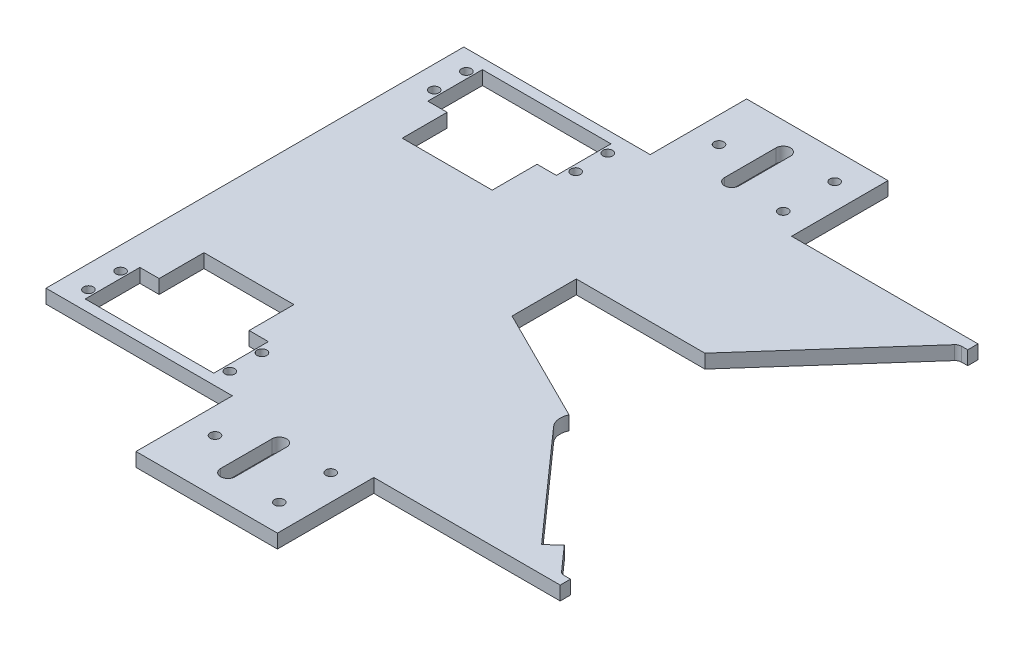
SolidWorks part; units mm, degrees
ref_plane "Front Plane" through (0, 0, 0) normal (0, 0, 1) x (1, 0, 0)
ref_plane "Top Plane" through (0, 0, 0) normal (0, 1, 0) x (1, 0, 0)
ref_plane "Right Plane" through (0, 0, 0) normal (1, 0, 0) x (0, 0, -1)
sketch "Sketch2" plane through (0, 0, 0) normal (0, 1, 0) x (1, 0, 0)
  line L2 (0, 0) -> (0, 65)
  line L3 (0, 65) -> (58, 65)
  line L4 (160, 0) -> (160, 65)
  line L8 (0, 0) -> (160, 0)
  line L9 (102, 65) -> (160, 65)
  line L11 (102, 65) -> (102, 95)
  line L12 (58, 65) -> (58, 95)
  line L13 (58, 95) -> (102, 95)
  dimension "D1" = 65
  dimension "D2" = 160
  dimension "D3" = 44
  dimension "D4" = 30
extrude "Boss-Extrude1" add sketch "Sketch2" along normal blind 4.3
mirror "Mirror1" about plane through (0, 4.3, 0) normal (0, 0, -1) of bodies 101
sketch "Sketch3" plane through (0, 4.3, 0) normal (0, 1, 0) x (1, 0, 0)
  line L0 (160, 61.8) -> (160, -61.8)
  line L1 (120.0126, 20) -> (157.1565, 61.8)
  line L3 (80.0126, 0) -> (80.0126, 20)
  line L4 (80.0126, 20) -> (120.0126, 20)
  line L12 (160, 65) -> (102, 65)
  line L13 (102, 65) -> (102, 95)
  line L15 (102, 95) -> (58, 95)
  line L16 (58, 65) -> (0, 65)
  line L17 (0, 65) -> (0, -65)
  line L18 (0, -65) -> (58, -65)
  line L20 (58, 95) -> (58, 65)
  line L22 (102, -65) -> (160, -65)
  line L23 (160, -65) -> (160, 65)
  line L36 (58, -65) -> (58, -95)
  line L38 (58, -95) -> (102, -95)
  line L39 (58, -95) -> (102, -95)
  line L40 (102, -95) -> (102, -65)
  line L42 (160, -61.8) -> (157.1556, -61.8)
  line L45 (160, 61.8) -> (157.1565, 61.8)
  line L48 (80.0126, 0) -> (120, -20)
  line L49 (120, -20) -> (157.1556, -61.8)
  line M24 (160, -65) -> (160, 65)
  dimension "D2" = 130
  dimension "D3" = 20
  dimension "D4" = 40
  dimension "D1" = 0
extrude "Cut-Extrude1" cut sketch "Sketch3" against normal blind 4.5 contours L48 L49 L1 L4 L3 M24 region at (132.7054, 4.3, -1.1594)
fillet "Fillet1" radius 2 2 edges at (157.1565, 2.15, -61.8) (157.1556, 2.15, 61.8)
ref_axis "Axis1" through (80, 4.3, 95) along (0, 0, -1)
sketch "Sketch4" plane through (0, 4.3, 0) normal (0, 1, 0) x (1, 0, 0)
  line L0 (80, -95) -> (80, 95)
  line L1 (102, -95) -> (58, -95) construction
  line L2 (102, 95) -> (58, 95) construction
ref_plane "Plane2" through (0, 4.3, 0) normal (0, 1, 0) x (1, 0, 0)
sketch "Sketch6" plane through (0, 4.3, 0) normal (0, 1, 0) x (1, 0, 0)
  line L3 (9, -61.8) -> (49, -61.8)
  line L6 (29, -45.8) -> (29, -44.8)
  line L7 (9, -44.8) -> (15, -44.8)
  line L11 (43, -44.8) -> (43, -30.8418)
  line L12 (15, -44.8) -> (15, -30.8418)
  line L13 (15, -30.8418) -> (43, -30.8418)
  line L15 (0, 0) -> (80.0126, 0)
  line L16 (80.0126, 0) -> (120, -20) construction
  line L18 (9, 44.8) -> (15, 44.8)
  line L20 (15, 30.8418) -> (43, 30.8418)
  line L21 (15, 44.8) -> (15, 30.8418)
  line L22 (43, 44.8) -> (43, 30.8418)
  line L25 (15, -45.8) -> (15, -30.8418) construction
  line L27 (9, 61.8) -> (49, 61.8)
  line L30 (4, -61.8) -> (3, -61.8)
  line L31 (0, -61.8) -> (160, -61.8) construction
  line L32 (3, -61.8) -> (4, -61.8)
  line L33 (3, -44.8) -> (3, -62.8) construction
  line L34 (3, -62.8) -> (55, -62.8) construction
  line L35 (55, -44.8) -> (55, -62.8) construction
  line L36 (4, -61.8) -> (54, -61.8) construction
  line L37 (0, 61.8) -> (160, 61.8) construction
  line L38 (54, 61.8) -> (55, 61.8)
  line L39 (54, 61.8) -> (55, 61.8)
  line L40 (43, 44.8) -> (49, 44.8)
  line L41 (4, -45.8) -> (4, -61.8) construction
  line L42 (4, -45.8) -> (54, -45.8) construction
  line L43 (43, -44.8) -> (49, -44.8)
  line L44 (3, -44.8) -> (55, -44.8) construction
  line L45 (29, -45.8) -> (29, -30.8418) construction
  line L46 (43, -45.8) -> (43, -30.8418) construction
  line L47 (54, -45.8) -> (54, -61.8) construction
  line L48 (9, -61.8) -> (49, -61.8)
  line L52 (9, 61.8) -> (9, 44.8)
  line L53 (55, 61.8) -> (54, 61.8)
  line L56 (49, 61.8) -> (49, 44.8)
  line L59 (3, -61.8) -> (4, -61.8)
  line L60 (9, -44.8) -> (9, -61.8)
  line L64 (49, -44.8) -> (49, -61.8)
  dimension "D4" = 1
  dimension "D5" = 14
  dimension "D6" = 14
extrude "Cut-Extrude2" cut sketch "Sketch6" against normal blind 10
sketch "Sketch7" plane through (0, 4.3, 0) normal (0, 1, 0) x (1, 0, 0)
  line L0 (0, 0) -> (80.0126, 0)
  line L1 (0, 65) -> (0, -65) construction
sketch "Sketch8" plane through (0, 4.3, 0) normal (0, 1, 0) x (1, 0, 0)
  circle A0 centre (7, 58.8) radius 1.5
  circle A1 centre (7, 48.8) radius 1.5
  circle A2 centre (51, 48.8) radius 1.5
  circle A3 centre (51, 58.8) radius 1.5
  circle A4 centre (7, -48.8) radius 1.5
  circle A5 centre (7, -58.8) radius 1.5
  circle A6 centre (51, -58.8) radius 1.5
  circle A7 centre (51, -48.8) radius 1.5
  dimension "D7" = 3
extrude "Cut-Extrude3" cut sketch "Sketch8" against normal blind 10
sketch "Sketch9" plane through (0, 0, 0) normal (0, -1, 0) x (1, 0, 0)
  line L0 (75.75, 70.4) -> (75.75, 86.4)
  line L1 (75.75, -86.4) -> (75.75, -70.4)
  line L2 (80.25, -86.4) -> (80.25, -70.4)
  line L4 (80.25, 70.4) -> (80.25, 86.4)
  circle A0 centre (94, 70.4) radius 1.5
  circle A1 centre (66, 78.4) radius 1.5
  circle A2 centre (66, -78.4) radius 1.5
  circle A3 centre (94, -86.4) radius 1.5
  circle A4 centre (94, 86.4) radius 1.5
  circle A5 centre (94, -70.4) radius 1.5
  arc A6 (75.75, -86.4) -> (80.25, -86.4) centre (78, -86.4) ccw
  arc A7 (80.25, -70.4) -> (75.75, -70.4) centre (78, -70.4) ccw
  arc A10 (75.75, 70.4) -> (80.25, 70.4) centre (78, 70.4) ccw
  arc A12 (80.25, 86.4) -> (75.75, 86.4) centre (78, 86.4) ccw
  dimension "D1" = 3
extrude "Cut-Extrude4" cut sketch "Sketch9" against normal blind 10
sketch "Sketch10" plane through (0, 4.3, 0) normal (0, 1, 0) x (1, 0, 0)
  line L0 (120, -20) -> (156.5589, -61.1287) construction
  line L1 (123.3218, -23.737) -> (149.8964, -53.6334)
  line L2 (116.263, -23.3218) -> (146.1593, -56.9552)
  line L3 (149.8964, -53.6334) -> (146.1593, -56.9552)
  line L4 (120, -20) -> (156.5589, -61.1287) construction
  line L5 (116.263, -23.3218) -> (152.8218, -64.4505) construction
  arc A0 (123.3218, -23.737) -> (116.263, -23.3218) centre (120, -20) ccw
  dimension "D1" = 5
  dimension "D2" = 45
extrude "Cut-Extrude5" cut sketch "Sketch10" against normal blind 10
